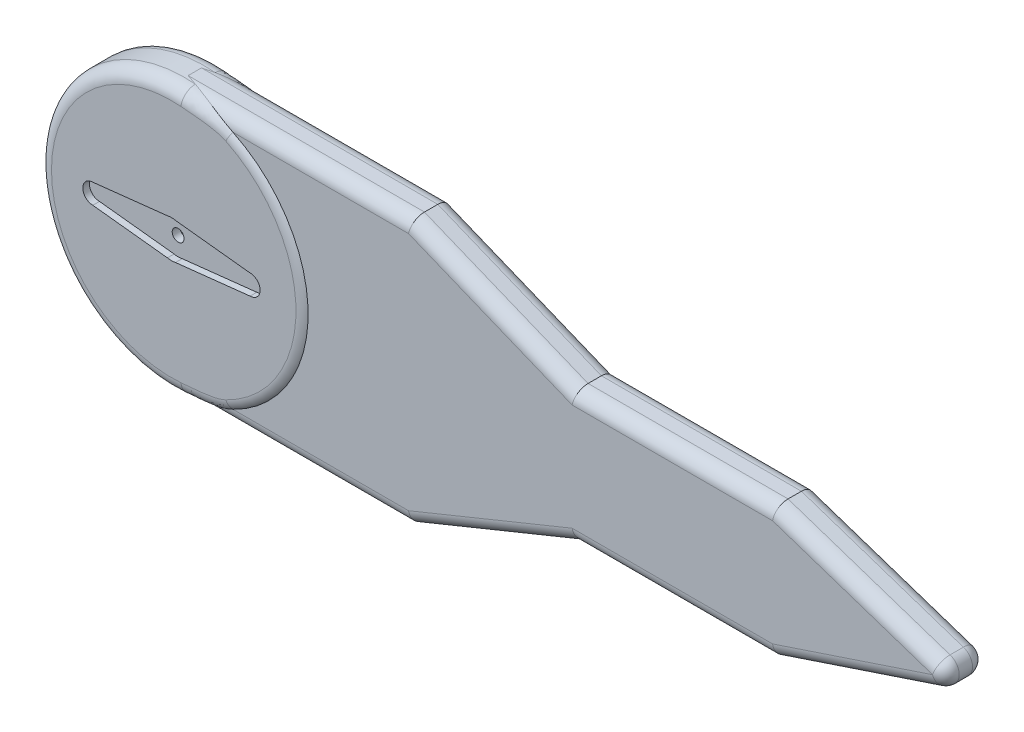
SolidWorks part; units mm, degrees
ref_plane "Front Plane" through (0, 0, 0) normal (0, 0, 1) x (1, 0, 0)
ref_plane "Top Plane" through (0, 0, 0) normal (0, 1, 0) x (1, 0, 0)
ref_plane "Right Plane" through (0, 0, 0) normal (1, 0, 0) x (0, 0, -1)
sketch "Sketch2" plane through (0, 0, 0) normal (0, 0, 1) x (1, 0, 0)
  line L0 (0, 25.4) -> (45.0271, 25.4)
  line L1 (45.0271, 25.4) -> (76.2, 12.7)
  line L2 (76.2, 12.7) -> (114.3, 12.7)
  line L4 (114.3, -12.7) -> (76.2, -12.7)
  line L5 (76.2, -12.7) -> (45.0271, -25.4)
  line L6 (45.0271, -25.4) -> (0, -25.4)
  line L7 (0, 0) -> (304.8, 0) construction
  line L8 (152.4, 0) -> (114.3, 12.7)
  line L9 (152.4, 0) -> (114.3, -12.7)
  circle A0 centre (0, 0) radius 25.4
  point P3 (0, 0)
  point P7 (0, 0)
  dimension "D1" = 50.8
  dimension "D2" = 152.4
  dimension "D3" = 33.6607
  dimension "D4" = 38.1
  dimension "D5" = 38.1
  dimension "D6" = 45.0271
extrude "Boss-Extrude1" add sketch "Sketch2" along normal mid plane 7.62 contours L7 A0 L6 L5 L4 | A0 L7 L2 L1 L0 region at (67.4972, 0, 0)
extrude "Boss-Extrude2" add sketch "Sketch2<3>" along normal mid plane 8.89 contours A0 region at (0, 0, 0)
sketch "Sketch2<3>" plane through (0, 0, 0) normal (0, 0, 1) x (1, 0, 0) same geometry as "Sketch2"
sketch "Sketch6" plane through (0, 0, 4.445) normal (0, 0, 1) x (1, 0, 0)
  line L0 (-14.986, 0) -> (14.986, 0) construction
  line L1 (0, -14.986) -> (0, 14.986) construction
  line L2 (-14.986, 1.905) -> (0, 3.556)
  line L3 (-14.986, -1.905) -> (0, -3.556)
  line L4 (14.986, -1.905) -> (0, -3.556)
  line L5 (14.986, 1.905) -> (0, 3.556)
  circle A0 centre (0, 0) radius 3.556
  circle A1 centre (-14.986, 0) radius 1.905
  circle A2 centre (14.986, 0) radius 1.905
  point P2 (0, 0)
  point P8 (0, 0)
  dimension "D3" = 7.112
  dimension "D4" = 3.81
  dimension "D1" = 29.972
  dimension "D2" = 29.972
extrude "Cut-Extrude1" cut sketch "Sketch6" against normal blind 1.27 contours A1 L3 A0 L2 | L4 A2 L5 A0 | A2 | A1 | A0 region at (-7.8269, 0, 4.445) region at (-14.986, 0, 4.445) region at (7.8269, 0, 4.445) region at (14.986, 0, 4.445)
sketch "Sketch11" plane through (0, 0, -4.445) normal (0, 0, -1) x (-1, 0, 0)
  point P0 (0, 0)
hole_wizard "CBORE for #1 Binding Head Machine Screw1" positions "Sketch11" profile "Sketch12" counterbore size "#1" standard "ANSI Inch" end condition through all
sketch "Sketch12" plane through (0, 0, -4.445) normal (1, 0, 0) x (0, 1, 0)
  line L0 (0, 0) -> (0, 8.89)
  line L1 (0, 8.89) -> (1.1303, 8.89)
  line L3 (1.1303, 8.89) -> (1.1303, 6.1214)
  line L4 (1.1303, 6.1214) -> (3.6512, 6.1214)
  line L5 (3.6512, 6.1214) -> (3.6513, 0)
  line L7 (3.6513, 0) -> (0, 0)
  line L11 (0, -6.35) -> (0, 107.95) construction
  dimension "Thru Hole Dia." = 2.2606
  dimension "Thru Hole Depth" = 8.89
  dimension "C'Bore Dia." = 7.3025
  dimension "C'Bore Depth" = 6.1214
fillet "Fillet1" radius 2.54 17 edges at (22.5135, -25.4, 3.81) (60.6135, -19.05, 3.81) (95.25, -12.7, 3.81) (22.5135, 25.4, 3.81) (60.6135, 19.05, 3.81) (95.25, 12.7, 3.81) (95.25, -12.7, -3.81) (60.6135, -19.05, -3.81) (22.5135, -25.4, -3.81) (22.5135, 25.4, -3.81) (60.6135, 19.05, -3.81) (95.25, 12.7, -3.81) (152.4, 0, 0) (133.35, -6.35, 3.81) (133.35, -6.35, -3.81) (133.35, 6.35, -3.81) (133.35, 6.35, 3.81)
fillet "Fillet2" radius 2.54 2 edges at (25.4, 0, 4.445) (25.4, 0, -4.445)
